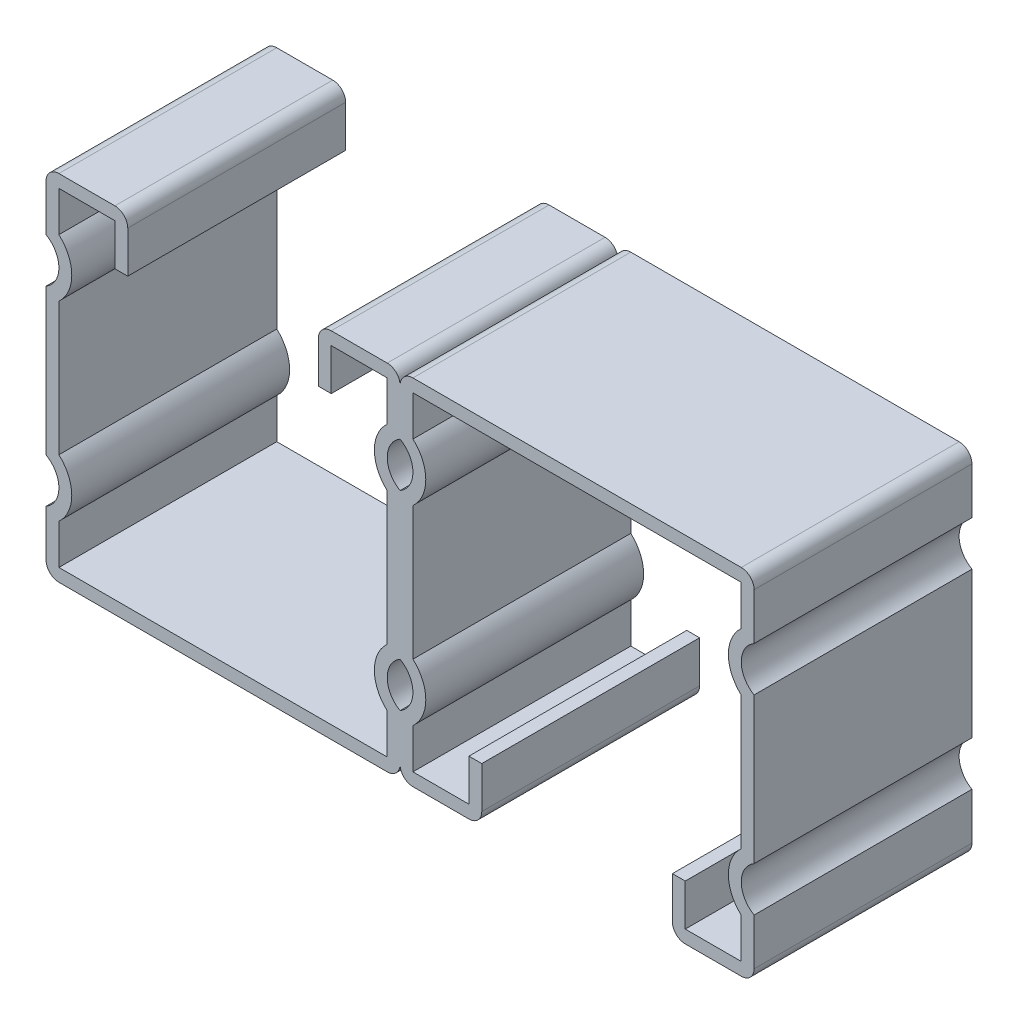
SolidWorks part; units mm, degrees
note: '?' marks a value the reader was unsure of.
ref_plane "Plane1" through (0, 0, 0) normal (0, 0, 1) x (1, 0, 0)
ref_plane "Plane2" through (0, 0, 0) normal (0, 1, 0) x (1, 0, 0)
ref_plane "Plane3" through (0, 0, 0) normal (1, 0, 0) x (0, 0, -1)
sketch "Sketch1" plane through (0, 0, 0) normal (0, 0, 1) x (1, 0, 0)
  line L0 (-41.275, 19.1389) -> (-41.275, 13.7082)
  line L1 (-41.275, 8.5168) -> (-41.275, -8.5168)
  line L2 (-39.7764, -20.6375) -> (-1.4986, -20.6375)
  line L3 (0, -19.1389) -> (0, -13.7082)
  line L4 (0, 13.7082) -> (0, 19.1389)
  line L5 (-1.4986, 20.6375) -> (-8.0264, 20.6375)
  line L6 (-9.525, 19.1389) -> (-9.525, 14.2875)
  line L7 (-39.7764, 20.6375) -> (-33.2486, 20.6375)
  line L8 (-31.75, 19.1389) -> (-31.75, 14.2875)
  line L9 (-1.4986, -14.4635) -> (-1.4986, 14.4635) construction
  line L10 (-39.7764, 14.4635) -> (-39.7764, -14.4635) construction
  line L11 (-33.2486, 19.1389) -> (-33.2486, 14.2875)
  line L12 (-39.7764, 19.1389) -> (-33.2486, 19.1389)
  line L13 (-39.7764, 19.1389) -> (-39.7764, 14.4635)
  line L14 (-39.7764, 7.7615) -> (-39.7764, -7.7615)
  line L15 (-39.7764, -19.1389) -> (-1.4986, -19.1389)
  line L16 (-1.4986, -19.1389) -> (-1.4986, -14.4635)
  line L17 (-1.4986, 14.4635) -> (-1.4986, 19.1389)
  line L18 (-1.4986, 19.1389) -> (-8.0264, 19.1389)
  line L19 (-8.0264, 19.1389) -> (-8.0264, 14.2875)
  line L20 (-33.2486, 14.2875) -> (-31.75, 14.2875)
  line L21 (-9.525, 14.2875) -> (-8.0264, 14.2875)
  line L22 (-10.16, 0) -> (12.7, 0) construction
  line L23 (-41.275, -13.7082) -> (-41.275, -19.1389)
  line L24 (-39.7764, -14.4635) -> (-39.7764, -19.1389)
  line L25 (0, -8.5168) -> (0, 8.5168)
  line L26 (-1.4986, -7.7615) -> (-1.4986, 7.7615)
  arc A0 (0, 13.7082) -> (0, 8.5168) centre (1.4986, 11.1125) ccw
  arc A1 (-41.275, 8.5168) -> (-41.275, 13.7082) centre (-42.7736, 11.1125) ccw
  arc A2 (-33.2486, 20.6375) -> (-31.75, 19.1389) centre (-33.2486, 19.1389) cw
  arc A3 (-41.275, 19.1389) -> (-39.7764, 20.6375) centre (-39.7764, 19.1389) cw
  arc A4 (-39.7764, -20.6375) -> (-41.275, -19.1389) centre (-39.7764, -19.1389) cw
  arc A5 (0, -19.1389) -> (-1.4986, -20.6375) centre (-1.4986, -19.1389) cw
  arc A6 (-1.4986, 20.6375) -> (0, 19.1389) centre (-1.4986, 19.1389) cw
  arc A7 (-9.525, 19.1389) -> (-8.0264, 20.6375) centre (-8.0264, 19.1389) cw
  arc A8 (-39.7764, 7.7615) -> (-39.7764, 14.4635) centre (-42.7736, 11.1125) ccw
  arc A9 (-1.4986, 14.4635) -> (-1.4986, 7.7615) centre (1.4986, 11.1125) ccw
  arc A10 (0, -13.7082) -> (0, -8.5168) centre (1.4986, -11.1125) cw
  arc A11 (-1.4986, -14.4635) -> (-1.4986, -7.7615) centre (1.4986, -11.1125) cw
  arc A12 (-39.7764, -7.7615) -> (-39.7764, -14.4635) centre (-42.7736, -11.1125) cw
  arc A13 (-41.275, -8.5168) -> (-41.275, -13.7082) centre (-42.7736, -11.1125) cw
  dimension "D9" = 2.9972
  dimension "D10" = 2.9972
  dimension "D6" = 22.225
  dimension "D2" = 9.525
extrude "Base-Extrude" add sketch "Sketch1" along normal mid plane 25.4
ref_axis "Axis1" through (0, 0, -50) along (0, 0, 1)?
pattern_circular "CirPattern1" count 2 every 180 about axis through (0, 0, 0) along (0, 0, 1) of "Base-Extrude"
equation "\"D6@Sketch1\" = \"Width@Sketch1\" - 2 * \"edge@Sketch1\""
equation "\"D10@Sketch1\" = 2 * \"gauge@Sketch1\""
equation "\"D9@Sketch1\" = \"D10@Sketch1\""
equation "\"D2@Sketch1\" = \"edge@Sketch1\""
